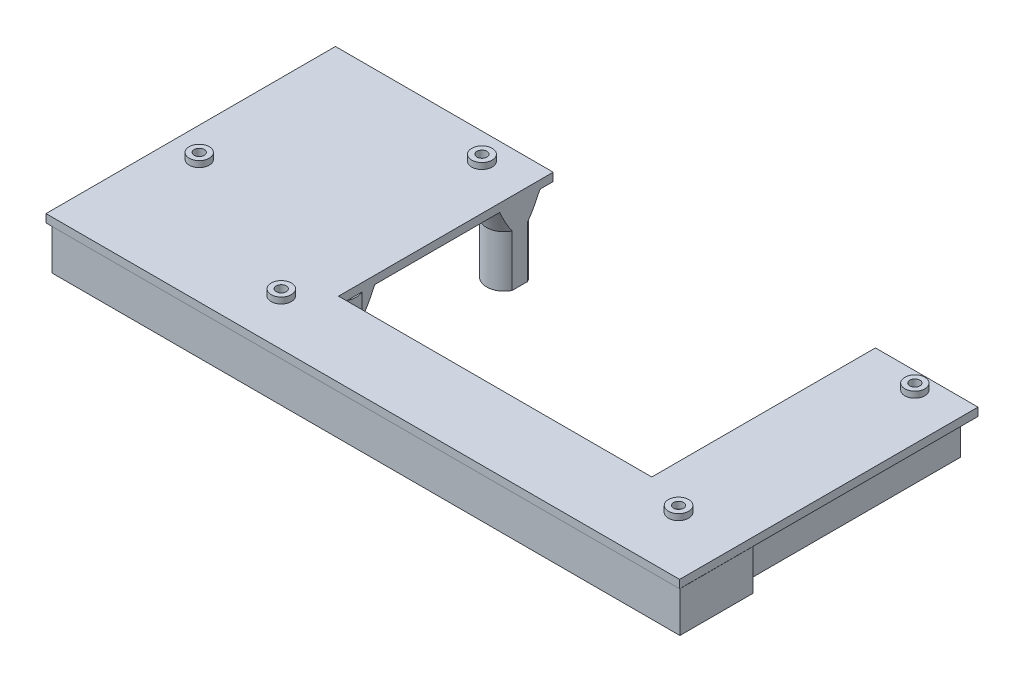
SolidWorks part; units mm, degrees
ref_plane "Plan de face" through (0, 0, 0) normal (0, 0, 1) x (1, 0, 0)
ref_plane "Plan de dessus" through (0, 0, 0) normal (0, 1, 0) x (1, 0, 0)
ref_plane "Plan de droite" through (0, 0, 0) normal (1, 0, 0) x (0, 0, -1)
sketch "Sketch1" plane through (0, 0, 0) normal (0, 1, 0) x (1, 0, 0)
  line L5 (0.5499, 6.4133) -> (-24.7496, 6.4133)
  line L6 (0.5499, 6.4133) -> (0.5499, -48.7457)
  line L7 (0.5499, -48.7457) -> (-24.7496, -48.7457)
  line L8 (-24.7496, 6.4133) -> (-24.7496, -48.7457)
  line L9 (0.5499, -48.7457) -> (-155.7253, -48.7457)
  line L10 (0.5499, -48.7457) -> (0.5499, -67.1873)
  line L11 (0.5499, -67.1873) -> (-155.7253, -67.1873)
  line L12 (-155.7253, -48.7457) -> (-155.7253, -67.1873)
  line L13 (-155.7253, -48.7457) -> (-102.0118, -48.7457)
  line L14 (-155.7253, -48.7457) -> (-155.7253, 4.2062)
  line L15 (-155.7253, 4.2062) -> (-102.0118, 4.2062)
  line L16 (-102.0118, -48.7457) -> (-102.0118, 4.2062)
  circle A0 centre (-10.8845, 2.272) radius 1.2417
  circle A1 centre (-13.8927, -53.0149) radius 1.2435
  circle A2 centre (-109.1393, -55.7413) radius 1.2446
  circle A3 centre (-148.3885, -36.7271) radius 1.2448
  circle A4 centre (-113.1482, -2.237) radius 1.2402
extrude "Boss-Extrude1" add sketch "Sketch1" along normal blind 2 contours L5 L8 L7 L6 A0 | L9 L12 L11 L10 L7 A2 A1 | L9 L16 L15 L14 A4 A3 region at (-12.1041, 0, 21.2478) region at (-77.642, 0, 57.9786) region at (-128.8618, 0, 22.2791)
sketch "Sketch2" plane through (0, 2, 0) normal (0, 1, 0) x (1, 0, 0)
  circle A0 centre (-113.1482, -2.237) radius 2.5218
  circle A1 centre (-113.1482, -2.237) radius 1.2402
  circle A2 centre (-148.3885, -36.7271) radius 2.4715
  circle A3 centre (-148.3885, -36.7271) radius 1.2448
  circle A4 centre (-109.1393, -55.7413) radius 2.4856
  circle A5 centre (-109.1393, -55.7413) radius 1.2446
  circle A6 centre (-13.8867, -53.0055) radius 2.5
  circle A7 centre (-13.8867, -53.0055) radius 1.2323
  circle A8 centre (-10.8845, 2.272) radius 1.2417
  circle A9 centre (-10.8845, 2.272) radius 2.4724
extrude "Boss-Extrude2" add sketch "Sketch2" along normal blind 1.5
sketch "Sketch3" plane through (0, 0, 0) normal (0, -1, 0) x (1, 0, 0)
  circle A0 centre (-105.8741, 4.0399) radius 2.1499
  circle A1 centre (-146.5741, 4.0399) radius 2.1499
  circle A2 centre (-146.5741, 44.7383) radius 2.1499
  circle A3 centre (-105.8741, 44.7383) radius 2.1499
  circle A4 centre (-105.8741, 44.7383) radius 4.265
  circle A5 centre (-146.5741, 44.7383) radius 4.265
  circle A6 centre (-146.5741, 4.0399) radius 4.2934
  circle A7 centre (-105.8741, 4.0399) radius 4.2934
  circle A8 centre (-146.5741, 4.0399) radius 1.25
  circle A9 centre (-105.8741, 4.0399) radius 1.25
  circle A10 centre (-105.8741, 44.7383) radius 1.25
  circle A11 centre (-146.5741, 44.7383) radius 1.25
  line M7 (-102.0118, -4.2062) -> (-102.0118, 48.7457)
  dimension "D1" = 2.5
  dimension "D2" = 2.5
  dimension "D3" = 2.5
  dimension "D4" = 2.5
extrude "Boss-Extrude3" add sketch "Sketch3" along normal blind 18.2 contours A10 | A7 A0 M7 | A0 A9 | A6 A1 | A1 A8 | A5 A2 | A2 A11 | A4 region at (-107.9632, 0, 4.0399) region at (-148.6632, 0, 4.0399) region at (-148.6632, 0, 44.7383) region at (-102.1302, 0, 4.0399) region at (-150.7184, 0, 44.7383) region at (-150.746, 0, 4.0399) region at (-105.8741, 0, 44.7383)
sketch "Sketch5" plane through (0, 0, 0) normal (0, -1, 0) x (1, 0, 0)
  line L0 (-20.9216, -4.0797) -> (-20.9216, 49.6266)
  line L1 (-18.9216, -2.0797) -> (-4.891, -2.0797)
  line L2 (-18.9216, -2.0797) -> (-18.9216, 47.6266)
  line L3 (-18.9216, 47.6266) -> (-4.891, 47.6266)
  line L4 (-4.891, -2.0797) -> (-4.891, 47.6266)
  line L5 (-3.4158, 51.1441) -> (-152.2279, 51.1441)
  line L6 (-3.4158, 51.1441) -> (-3.4158, 65.1441)
  line L7 (-3.4158, 65.1441) -> (-152.2279, 65.1441)
  line L8 (-152.2279, 51.1441) -> (-152.2279, 65.1441)
  line L9 (-20.9216, 49.6266) -> (-2.891, 49.6266)
  line L10 (-2.891, -4.0797) -> (-2.891, 49.6266)
  line L11 (-20.9216, -4.0797) -> (-2.891, -4.0797)
  line L12 (-1.4158, 49.1441) -> (-1.4158, 67.1441)
  line L13 (-1.4158, 67.1441) -> (-154.2279, 67.1441)
  line L14 (-154.2279, 49.1441) -> (-154.2279, 67.1441)
  line L15 (-1.4158, 49.1441) -> (-154.2279, 49.1441)
  circle M15 centre (-10.8845, -2.272) radius 1.2417
  circle M16 centre (-109.1393, 55.7413) radius 1.2446
  circle M17 centre (-13.8927, 53.0149) radius 1.2435
  dimension "D1" = 2
  dimension "D2" = 2
extrude "Boss-Extrude4" add sketch "Sketch5" along normal blind 10 contours L10 L15 L0 L11 L4 L1 L2 L3 M15 | L8 L5 L6 L7 M17 M16 | L15 L14 L13 L12 region at (-20.3597, 0, 22.5322) region at (-77.8981, 0, 58.1618)
sketch "Sketch7" plane through (0, 0, 0) normal (0, -1, 0) x (1, 0, 0)
  line L1 (-20.9216, -4.0797) -> (-2.891, -4.0797)
  line L2 (-20.9216, -4.0797) -> (-20.9216, -5.5593)
  line L3 (-20.9216, -5.5593) -> (-2.891, -5.5593)
  line L4 (-2.891, -4.0797) -> (-2.891, -5.5593)
extrude "Boss-Extrude5" add sketch "Sketch7" along normal up to surface (10 mm away) up to face at (-11.5657, -10, 14.2501)
sketch "Sketch8" plane through (0, 0, 0) normal (0, -1, 0) x (1, 0, 0)
  line L1 (-18.9216, -3.5797) -> (-4.891, -3.5797)
  line L2 (-18.9216, -3.5797) -> (-18.9216, -4.5797)
  line L3 (-18.9216, -4.5797) -> (-4.891, -4.5797)
  line L4 (-4.891, -3.5797) -> (-4.891, -4.5797)
  line L6 (-18.9216, -2.0797) -> (-12.1111, -2.0797) construction
  circle A0 centre (-10.8845, -2.272) radius 2.5
  arc M4 (-12.1111, -2.0797) -> (-9.6578, -2.0797) centre (-10.8845, -2.272) cw
  line M5 (-9.6578, -2.0797) -> (-4.891, -2.0797)
  line M9 (-18.9216, -2.0797) -> (-12.1111, -2.0797)
  dimension "D1" = 5
  dimension "D2" = 1
  dimension "D3" = 1.5
extrude "Cut-Extrude1" cut sketch "Sketch8" along normal blind 16.42 contours A0 M5 M9 M4 | L1 A0 M5 M4 M9 | L3 L4 L1 L2 | A0 region at (-10.8845, 0, -2.5616) region at (-10.8845, 0, -0.9561)
sketch "Sketch9" plane through (0, 0, 0) normal (0, -1, 0) x (1, 0, 0)
  line L1 (-1.4158, 67.1441) -> (0.5842, 67.1441)
  line L2 (-1.4158, 67.1441) -> (-1.4158, 49.1441)
  line L3 (-1.4158, 49.1441) -> (0.5842, 49.1441)
  line L4 (0.5842, 67.1441) -> (0.5842, 49.1441)
  dimension "D1" = 2
extrude "Boss-Extrude6" add sketch "Sketch9" along normal up to surface (10 mm away) up to face at (-44.8641, -10, 39.9683)
sketch "Sketch10" plane through (0, -10, 0) normal (0, -1, 0) x (1, 0, 0)
  line L0 (-3.4158, 51.1441) -> (-3.4158, 65.1441) construction
  line L1 (-1.9158, 65.1441) -> (-0.9158, 65.1441)
  line L2 (-1.9158, 65.1441) -> (-1.9158, 51.1441)
  line L3 (-1.9158, 51.1441) -> (-0.9158, 51.1441)
  line L4 (-0.9158, 65.1441) -> (-0.9158, 51.1441)
  line L5 (-3.4158, 65.1441) -> (-152.2279, 65.1441) construction
  line L6 (-3.4158, 60.6441) -> (-1.9158, 60.6441)
  line L7 (-3.4158, 60.6441) -> (-3.4158, 55.6441)
  line L8 (-3.4158, 55.6441) -> (-1.9158, 55.6441)
  line L9 (-1.9158, 60.6441) -> (-1.9158, 55.6441)
  line M15 (-3.4158, 65.1441) -> (-3.4158, 51.1441)
  dimension "D1" = 1
  dimension "D2" = 1.5
  dimension "D3" = 5
  dimension "D4" = 4.5
extrude "Cut-Extrude2" cut sketch "Sketch10" against normal up to surface (10 mm away) contours L4 L1 L2 L3 | L8 L2 L6 M15 region at (-1.4158, -10, 58.1441) region at (-2.6658, -10, 58.1441) up to face at (-146.5741, 0, 49.0033)
chamfer "Chamfer1" distance 2 angle 70 4 edges at (-146.5741, 0, 49.0033) (-146.5741, 0, 8.3333) (-110.1674, 0, 4.0399) (-110.1391, 0, 44.7383) first distance on face at (-146.5741, 0, 49.0033)
sketch "Sketch12" plane through (0, 0, 0) normal (0, -1, 0) x (1, 0, 0)
  line L0 (-19.4216, 48.1266) -> (-19.4216, -2.5797)
  line L1 (-18.9216, 47.6266) -> (-4.891, 47.6266)
  line L2 (-18.9216, 47.6266) -> (-18.9216, -2.0797)
  line L3 (-18.9216, -2.0797) -> (-4.891, -2.0797)
  line L4 (-4.891, 47.6266) -> (-4.891, -2.0797)
  line L5 (-19.4216, -2.5797) -> (-4.391, -2.5797)
  line L6 (-4.391, 48.1266) -> (-4.391, -2.5797)
  line L7 (-19.4216, 48.1266) -> (-4.391, 48.1266)
  line L16 (-152.7279, 65.6441) -> (-152.7279, 50.6441)
  line L17 (-152.2279, 65.1441) -> (-3.4158, 65.1441)
  line L18 (-152.2279, 65.1441) -> (-152.2279, 51.1441)
  line L19 (-152.2279, 51.1441) -> (-3.4158, 51.1441)
  line L20 (-3.4158, 65.1441) -> (-3.4158, 51.1441)
  line L21 (-152.7279, 50.6441) -> (-2.9158, 50.6441)
  line L22 (-2.9158, 65.6441) -> (-2.9158, 50.6441)
  line L23 (-152.7279, 65.6441) -> (-2.9158, 65.6441)
  dimension "D1" = 0.5
  dimension "D2" = 0.5
extrude "Cut-Extrude3" cut sketch "Sketch12" along normal blind 16.42
sketch "Sketch13" plane through (0, 0, 0) normal (0, -1, 0) x (-1, 0, 0)
  circle A0 centre (127.4316, -24.7592) radius 17.9838
extrude "Boss-Extrude7" add sketch "Sketch13" along normal blind 2
